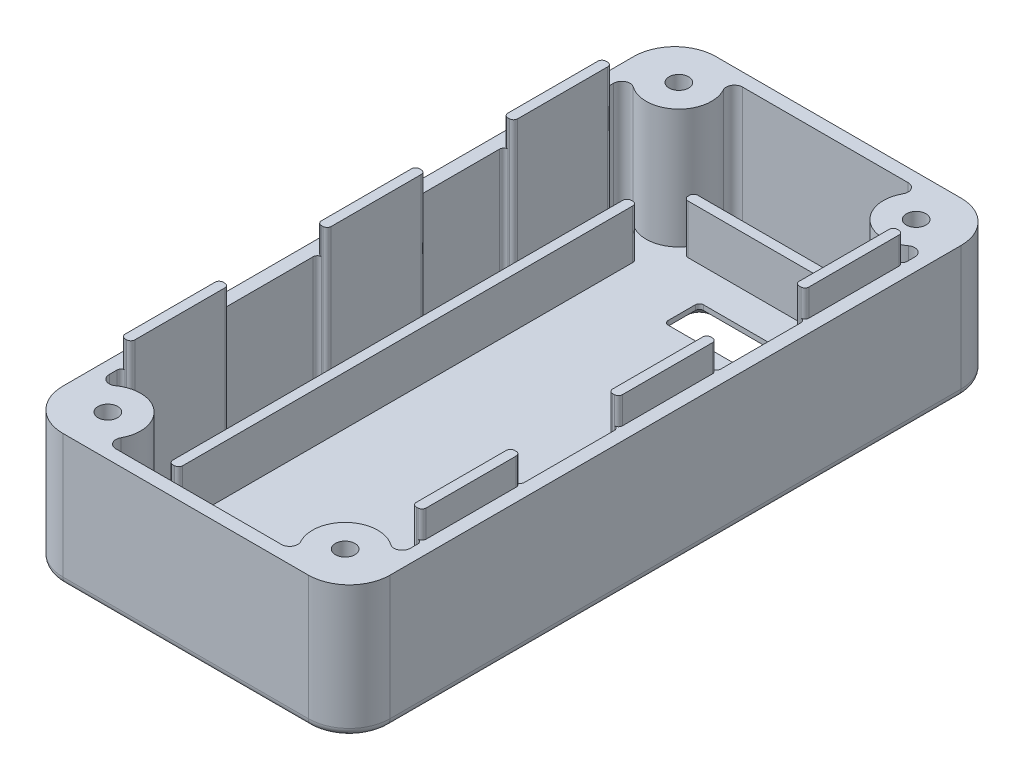
SolidWorks part; units mm, degrees
ref_plane "Front Plane" through (0, 0, 0) normal (0, 0, 1) x (1, 0, 0)
ref_plane "Top Plane" through (0, 0, 0) normal (0, 1, 0) x (1, 0, 0)
ref_plane "Right Plane" through (0, 0, 0) normal (1, 0, 0) x (0, 0, -1)
sketch "Base Sketch" plane through (0, 0, 0) normal (0, 1, 0) x (1, 0, 0)
  line L1 (0, 0) -> (40, 0)
  line L2 (0, 0) -> (0, 79.79)
  line L3 (0, 79.79) -> (40, 79.79)
  line L4 (40, 0) -> (40, 79.79)
extrude "Base" add sketch "Base Sketch" along normal blind 16.2
fillet "Corner Rounds R5" radius 5 4 edges at (0, 8.1, -79.79) (40, 8.1, -79.79) (40, 8.1, 0) (0, 8.1, 0)
shell "Shell" thickness 1.6 removed face at (20, 16.2, -39.895)
sketch "Sketch2" plane through (0, 0, 0) normal (0, 1, 0) x (1, 0, 0)
  circle A0 centre (5.5, 5) radius 4
  circle A1 centre (34.5, 5) radius 4
  circle A2 centre (5.5, 74.79) radius 4
  circle A3 centre (34.5, 74.79) radius 4
extrude "Screw Bosses" add sketch "Sketch2" along normal blind 16.2
sketch "Sketch3" plane through (0, 0, 0) normal (0, 1, 0) x (1, 0, 0)
  line L1 (1.6, 10.5) -> (2.8, 10.5)
  line L2 (1.6, 10.5) -> (1.6, 22.5)
  line L3 (1.6, 22.5) -> (2.8, 22.5)
  line L4 (2.8, 10.5) -> (2.8, 22.5)
  line L6 (1.6, 34.5) -> (2.8, 34.5)
  line L7 (1.6, 34.5) -> (1.6, 46.5)
  line L8 (1.6, 46.5) -> (2.8, 46.5)
  line L9 (2.8, 34.5) -> (2.8, 46.5)
  line L11 (1.6, 57.29) -> (2.8, 57.29)
  line L12 (1.6, 57.29) -> (1.6, 69.29)
  line L13 (1.6, 69.29) -> (2.8, 69.29)
  line L14 (2.8, 57.29) -> (2.8, 69.29)
  line L16 (37.2, 10.5) -> (38.4, 10.5)
  line L17 (37.2, 10.5) -> (37.2, 22.5)
  line L18 (37.2, 22.5) -> (38.4, 22.5)
  line L19 (38.4, 10.5) -> (38.4, 22.5)
  line L21 (37.2, 34.5) -> (38.4, 34.5)
  line L22 (37.2, 34.5) -> (37.2, 46.5)
  line L23 (37.2, 46.5) -> (38.4, 46.5)
  line L24 (38.4, 34.5) -> (38.4, 46.5)
  line L26 (37.2, 57.29) -> (38.4, 57.29)
  line L27 (37.2, 57.29) -> (37.2, 69.29)
  line L28 (37.2, 69.29) -> (38.4, 69.29)
  line L29 (38.4, 57.29) -> (38.4, 69.29)
extrude "Alignment Tabs" add sketch "Sketch3" along normal blind 19.5
fillet "Bottom Edge Round R1" radius 1 8 edges at (1.4645, 0, -1.4645) (20, 0, 0) (38.5355, 0, -1.4645) (40, 0, -39.895) (38.5355, 0, -78.3255) (20, 0, -79.79) (1.4645, 0, -78.3255) (0, 0, -39.895)
sketch "Sketch4" plane through (0, 0, 0) normal (0, 1, 0) x (1, 0, 0)
  circle A0 centre (5.5, 5) radius 1.2
  circle A1 centre (34.5, 5) radius 1.2
  circle A2 centre (5.5, 74.79) radius 1.2
  circle A3 centre (34.5, 74.79) radius 1.2
extrude "M2 Clearance Holes" cut sketch "Sketch4" along normal through all
sketch "Sketch5" plane through (0, 0, 0) normal (0, 1, 0) x (1, 0, 0)
  circle A0 centre (5.5, 5) radius 2.2
  circle A1 centre (34.5, 5) radius 2.2
  circle A2 centre (5.5, 74.79) radius 2.2
  circle A3 centre (34.5, 74.79) radius 2.2
extrude "M2 Counterbores" cut sketch "Sketch5" along normal blind 12.2
sketch "Slide Switch Cutout Sketch" plane through (0, 0, 0) normal (0, 1, 0) x (1, 0, 0)
  line L0 (16.2, 63.4) -> (23.8, 63.4)
  line L1 (23.8, 63.4) -> (23.8, 67)
  line L2 (23.8, 67) -> (16.2, 67)
  line L3 (16.2, 67) -> (16.2, 63.4)
extrude "Slide Switch Cutout" cut sketch "Slide Switch Cutout Sketch" along normal blind 2
sketch "2xAAA Guide Rails Sketch" plane through (0, 0, 0) normal (0, 1, 0) x (1, 0, 0)
  line L0 (32.85, 12) -> (34.05, 12)
  line L1 (34.05, 12) -> (34.05, 68)
  line L2 (34.05, 68) -> (32.85, 68)
  line L3 (32.85, 68) -> (32.85, 12)
  line L4 (5.95, 12) -> (7.15, 12)
  line L5 (7.15, 12) -> (7.15, 68)
  line L6 (7.15, 68) -> (5.95, 68)
  line L7 (5.95, 68) -> (5.95, 12)
extrude "2xAAA Guide Rails" add sketch "2xAAA Guide Rails Sketch" along normal blind 7.6
sketch "2xAAA End Rails Sketch" plane through (0, 0, 0) normal (0, 1, 0) x (1, 0, 0)
  line L0 (9.5, 7.2) -> (30.5, 7.2)
  line L1 (30.5, 7.2) -> (30.5, 8.4)
  line L2 (30.5, 8.4) -> (9.5, 8.4)
  line L3 (9.5, 8.4) -> (9.5, 7.2)
  line L4 (9.5, 71.4) -> (30.5, 71.4)
  line L5 (30.5, 71.4) -> (30.5, 72.6)
  line L6 (30.5, 72.6) -> (9.5, 72.6)
  line L7 (9.5, 72.6) -> (9.5, 71.4)
extrude "2xAAA End Rails" add sketch "2xAAA End Rails Sketch" along normal blind 7.6
chamfer "Rail Buttress Chamfers 3x45" distance 3 angle 45 4 edges at (20, 1.6, -72.6) (20, 1.6, -7.2) (5.95, 1.6, -40) (34.05, 1.6, -40) tangent propagation no
fillet "Lug Junction Fillets R1" radius 1 8 edges at (32.3929, 8.9, -78.19) (38.4, 8.9, -73.9012) (7.6071, 8.9, -78.19) (1.6, 8.9, -73.9012) (32.3929, 8.9, -1.6) (38.4, 8.9, -5.8888) (7.6071, 8.9, -1.6) (1.6, 8.9, -5.8888)
chamfer "Chamfer2" distance 1 angle 45 3 edges at (5.5, 12.2, -2.8) (34.5, 12.2, -2.8) (34.5, 12.2, -72.59)
fillet "Fillet2" radius 0.5 44 edges at (37.2, 10.55, -69.29) (38.4, 8.9, -69.29) (32.85, 4.6, -68) (32.85, 4.6, -12) (30.5, 4.6, -71.4) (30.5, 4.6, -8.4) (9.5, 4.6, -71.4) (9.5, 4.6, -8.4) (7.15, 4.6, -68) (7.15, 4.6, -12) (34.05, 6.1, -68) (34.05, 6.1, -12) (30.5, 6.1, -72.6) (30.5, 6.1, -7.2) (9.5, 6.1, -72.6) (9.5, 6.1, -7.2) (5.95, 6.1, -68) (5.95, 6.1, -12) (23.8, 0.8, -67) (23.8, 0.8, -63.4) (16.2, 0.8, -67) (16.2, 0.8, -63.4) (37.2, 10.55, -57.29) (37.2, 10.55, -46.5) (37.2, 10.55, -34.5) (37.2, 10.55, -22.5) (37.2, 10.55, -10.5) (2.8, 10.55, -69.29) (2.8, 10.55, -57.29) (2.8, 10.55, -46.5) (2.8, 10.55, -34.5) (2.8, 10.55, -22.5) (2.8, 10.55, -10.5) (38.4, 8.9, -57.29) (38.4, 8.9, -46.5) (38.4, 8.9, -34.5) (38.4, 8.9, -22.5) (38.4, 8.9, -10.5) (1.6, 8.9, -69.29) (1.6, 8.9, -57.29) (1.6, 8.9, -46.5) (1.6, 8.9, -34.5) (1.6, 8.9, -22.5) (1.6, 8.9, -10.5)
fillet "Tab Top Corner Fillets R0.5" radius 0.5 12 edges at (38.4, 17.85, -57.29) (38.4, 17.85, -69.29) (38.4, 17.85, -34.5) (38.4, 17.85, -46.5) (38.4, 17.85, -10.5) (38.4, 17.85, -22.5) (1.6, 17.85, -57.29) (1.6, 17.85, -69.29) (1.6, 17.85, -34.5) (1.6, 17.85, -46.5) (1.6, 17.85, -22.5) (1.6, 17.85, -10.5)
sketch "Slide Switch Slot Sketch" plane through (0, 0, 0) normal (0, 1, 0) x (1, 0, 0)
  line L0 (15.94, 63.04) -> (24.06, 63.04)
  line L1 (24.56, 63.54) -> (24.56, 66.86)
  line L2 (24.06, 67.36) -> (15.94, 67.36)
  line L3 (15.44, 66.86) -> (15.44, 63.54)
  arc A0 (24.06, 63.04) -> (24.56, 63.54) centre (24.06, 63.54) ccw
  arc A1 (24.56, 66.86) -> (24.06, 67.36) centre (24.06, 66.86) ccw
  arc A2 (15.94, 67.36) -> (15.44, 66.86) centre (15.94, 66.86) ccw
  arc A3 (15.44, 63.54) -> (15.94, 63.04) centre (15.94, 63.54) ccw
extrude "Slide Switch Slot +20% 9.12x4.32" cut sketch "Slide Switch Slot Sketch" along normal through all
chamfer "Slot Chamfer 1x45 (support-free)" distance 1 angle 45 8 edges at (15.5864, 0, -63.1864) (20, 0, -63.04) (24.4136, 0, -63.1864) (24.56, 0, -65.2) (24.4136, 0, -67.2136) (20, 0, -67.36) (15.5864, 0, -67.2136) (15.44, 0, -65.2)
